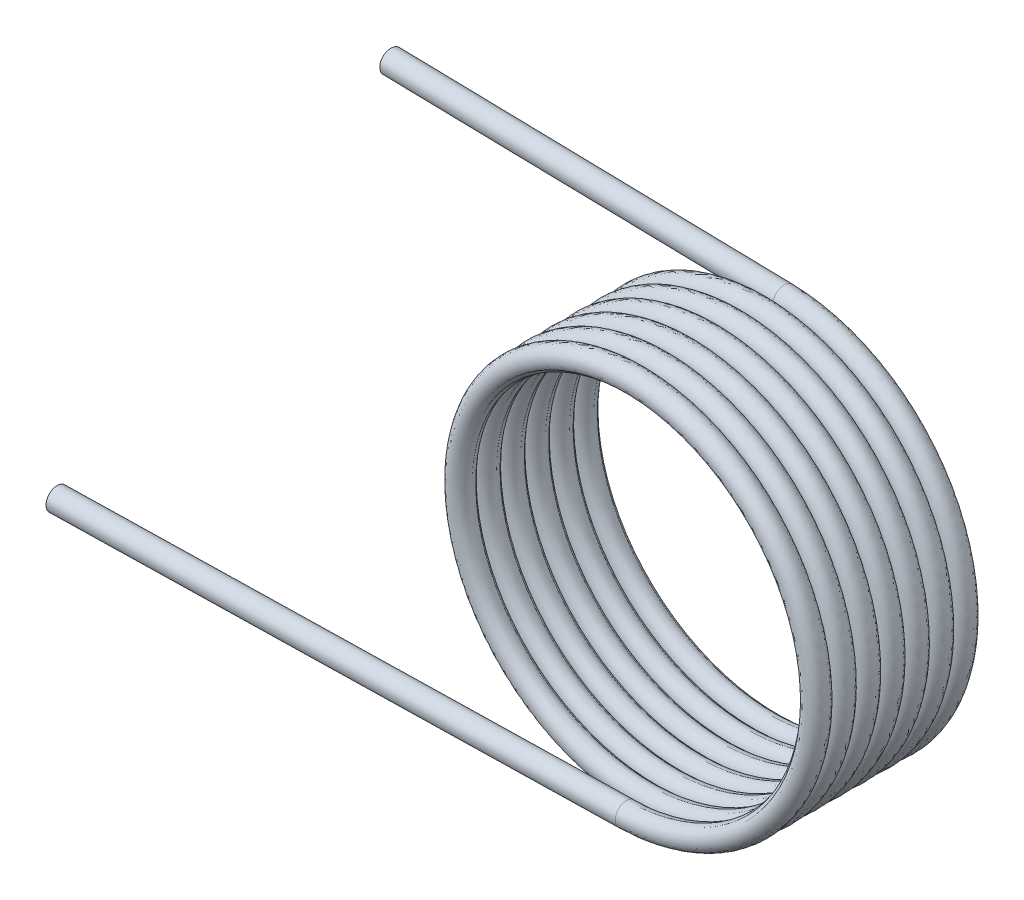
SolidWorks part; units mm, degrees
material "music wire"
ref_plane "Front Plane" through (0, 0, 0) normal (0, 0, 1) x (1, 0, 0)
ref_plane "Top Plane" through (0, 0, 0) normal (0, 1, 0) x (1, 0, 0)
ref_plane "Right Plane" through (0, 0, 0) normal (1, 0, 0) x (0, 0, -1)
sketch "Sketch1" plane through (0, 0, 0) normal (0, 0, 1) x (1, 0, 0)
  circle A0 centre (0, 0) radius 23.6029
  dimension "D1" = 47.2059
curve "Helix/Spiral1" pitch 3.1262 height 20.32 radius 23.6029 left hand yes centre (0, 0, 0) axis (0, 0, 1) start towards (0, 1, 0)
ref_plane "Plane1" through (0, -23.6029, 20.32) normal (-0.9998, 0, 0.0211) x (0.0211, 0, 0.9998)
sketch "Sketch2" plane through (0, -23.6029, 20.32) normal (-0.9998, 0, 0.0211) x (0.0211, 0, 0.9998)
  circle A1 centre (0, 0) radius 1.4351
  dimension "D1" = 2.8702
sweep "Sweep1" add profiles "Sketch2" path "Helix/Spiral1"
sketch "Sketch3" plane through (0, 0, 0) normal (-0.9998, 0, -0.0211) x (-0.0211, 0, 0.9998)
  circle A0 centre (0, 23.6029) radius 1.4351 construction
  circle A1 centre (0, 23.6029) radius 1.4351
extrude "Boss-Extrude1" add sketch "Sketch3" along normal blind 101.6
sketch "Sketch4" plane through (-0.4281, 0, 0.009) normal (-0.9998, 0, 0.0211) x (0.0211, 0, 0.9998)
  circle A0 centre (20.3155, -23.603) radius 1.4351 construction
  circle A1 centre (20.3155, -23.603) radius 1.4351
extrude "Boss-Extrude2" add sketch "Sketch4" along normal blind 101.6
sketch "Sketch5" plane through (-101.5774, 0, -2.1412) normal (-0.9998, 0, -0.0211) x (-0.0211, 0, 0.9998)
  circle A0 centre (0, 23.6029) radius 5.7146
extrude "Cut-Extrude1" cut sketch "Sketch5" against normal blind 50
sketch "Sketch6" plane through (-102.0056, 0, 2.1502) normal (-0.9998, 0, 0.0211) x (0.0211, 0, 0.9998)
  circle A0 centre (20.3155, -23.6029) radius 6.6279
extrude "Cut-Extrude2" cut sketch "Sketch6" against normal blind 30
ref_axis "Axis1" through (0, 0, 24.5531) along (0, 0, -1)
